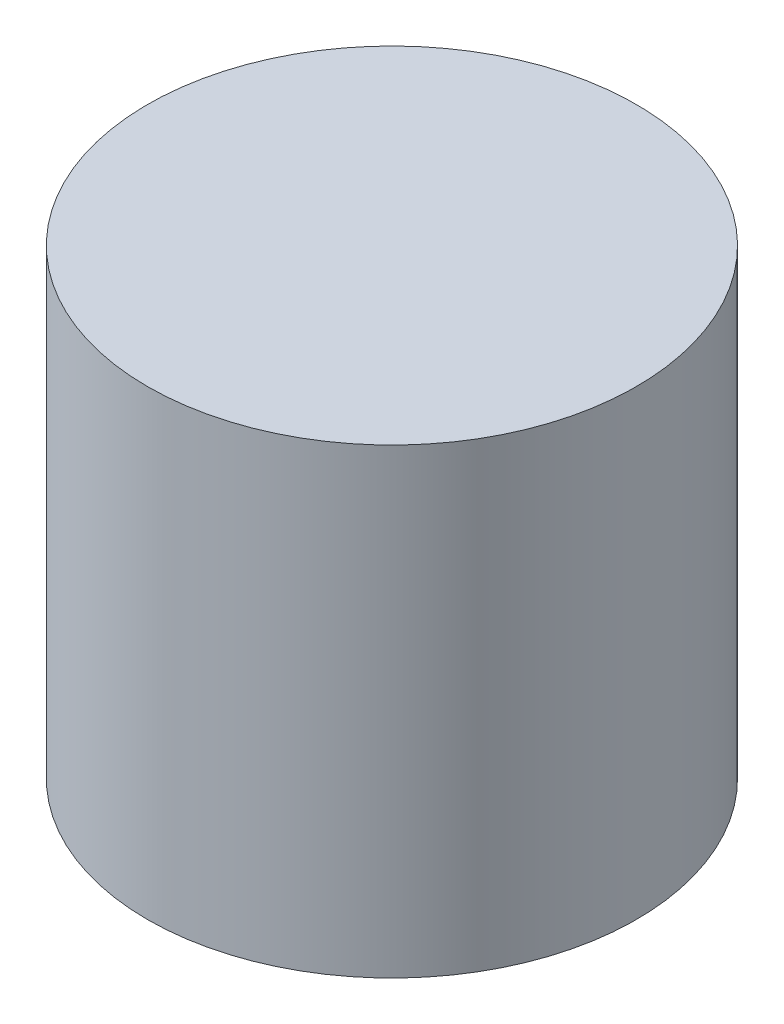
SolidWorks part; units mm, degrees
material "Commercially Pure CP-Ti UNS R50400 (SS)"
ref_plane "Front Plane" through (0, 0, 0) normal (0, 0, 1) x (1, 0, 0)
ref_plane "Top Plane" through (0, 0, 0) normal (0, 1, 0) x (1, 0, 0)
ref_plane "Right Plane" through (0, 0, 0) normal (1, 0, 0) x (0, 0, -1)
sketch "Sketch1" plane through (0, 0, 0) normal (0, 1, 0) x (1, 0, 0)
  circle A0 centre (0, 0) radius 22.86
  dimension "D1" = 45.72
extrude "Boss-Extrude1" add sketch "Sketch1" along normal blind 43.18
sketch "Sketch3" plane through (0, 0, 0) normal (0, -1, 0) x (-1, 0, 0)
  circle A0 centre (0, 11.43) radius 3.81
  dimension "D1" = 7.62
  dimension "D2" = 11.43
ref_axis "Axis1" through (0, 43.18, 0) along (0, -1, 0)
extrude "Boss-Extrude2" add sketch "Sketch3" along normal blind 2.54 draft 52
pattern_circular "CirPattern1" count 8 over 360 about axis through (0, 43.18, 0) along (0, -1, 0) of "Boss-Extrude2"
